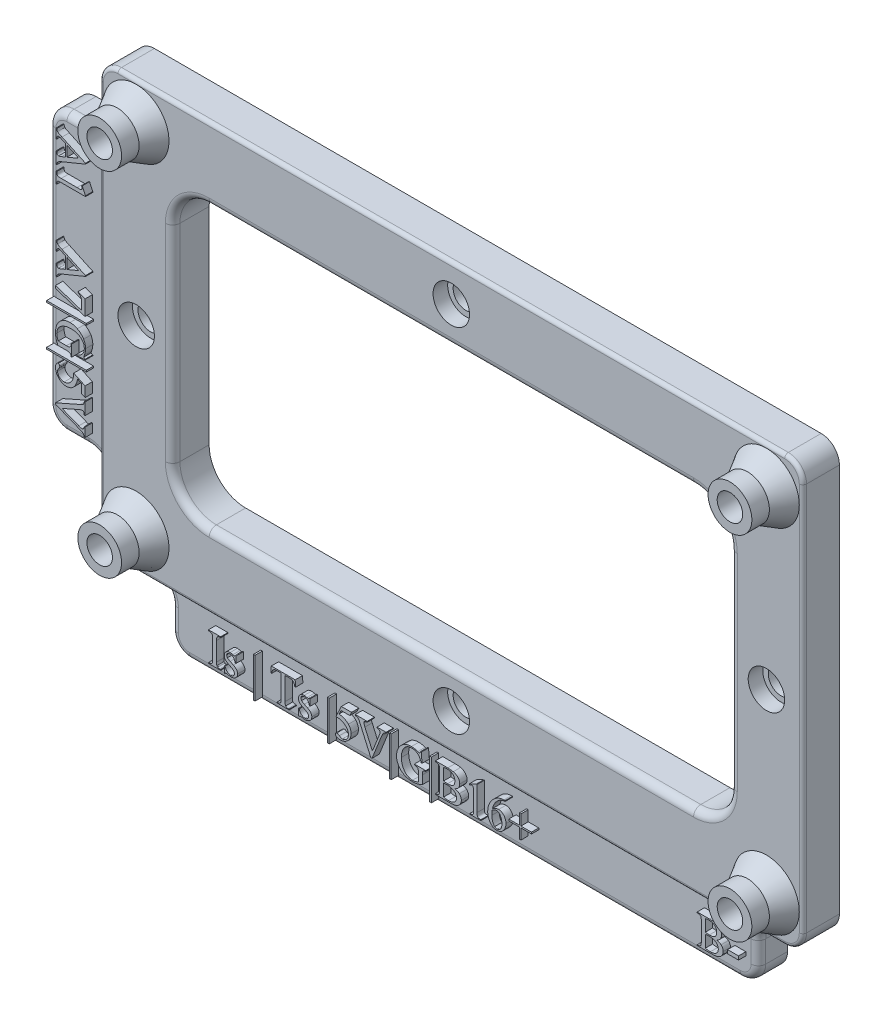
SolidWorks part; units mm, degrees
ref_plane "Front Plane" through (0, 0, 0) normal (0, 0, 1) x (1, 0, 0)
ref_plane "Top Plane" through (0, 0, 0) normal (0, 1, 0) x (1, 0, 0)
ref_plane "Right Plane" through (0, 0, 0) normal (1, 0, 0) x (0, 0, -1)
sketch "Sketch1" plane through (0, 0, 0) normal (0, 0, 1) x (1, 0, 0)
  line L0 (-5, 53.3) -> (91.4, 53.3)
  line L1 (91.4, 53.3) -> (91.4, -5)
  line L2 (91.4, -5) -> (-5, -5)
  line L3 (-5, -5) -> (-5, 53.3)
  line L4 (5, 43.3) -> (5, 5)
  line L5 (5, 5) -> (81.4, 5)
  line L6 (81.4, 5) -> (81.4, 43.3)
  line L7 (81.4, 43.3) -> (5, 43.3)
  circle A0 centre (0, 0) radius 1.75
  circle A1 centre (86.4, 0) radius 1.75
  circle A2 centre (0, 48.3) radius 1.75
  circle A3 centre (86.4, 48.3) radius 1.75
  circle A4 centre (0, 24.15) radius 1.75
  circle A5 centre (43.2, 48.3) radius 1.75
  circle A6 centre (86.4, 24.15) radius 1.75
  circle A7 centre (43.2, 0) radius 1.75
  point P26 (-5, 24.15)
  point P28 (43.2, 53.3)
  point P30 (43.2, -5)
  point P32 (91.4, 24.15)
  dimension "D1" = 3.5
  dimension "D2" = 3.5
  dimension "D3" = 3.5
  dimension "D4" = 3.5
  dimension "D15" = 3.5
  dimension "D16" = 3.5
  dimension "D17" = 3.5
  dimension "D18" = 3.5
  dimension "D5" = 86.4
  dimension "D6" = 48.3
  dimension "D7" = 5
  dimension "D8" = 5
  dimension "D9" = 5
  dimension "D10" = 5
  dimension "D11" = 10
  dimension "D12" = 10
  dimension "D13" = 10
  dimension "D14" = 10
  dimension "D19" = 5
  dimension "D20" = 5
  dimension "D21" = 5
  dimension "D22" = 5
extrude "Boss-Extrude1" add sketch "Sketch1" along normal blind 5
sketch "Sketch2" plane through (0, 0, 5) normal (0, 0, 1) x (1, 0, 0)
  circle A0 centre (0, 48.3) radius 1.75
  circle A1 centre (0, 48.3) radius 3
  circle A2 centre (86.4, 48.3) radius 1.75
  circle A3 centre (86.4, 48.3) radius 3
  circle A4 centre (86.4, 0) radius 1.75
  circle A5 centre (86.4, 0) radius 3
  circle A6 centre (0, 0) radius 1.75
  circle A7 centre (0, 0) radius 3
  dimension "D1" = 3.5
  dimension "D2" = 3.5
  dimension "D3" = 3.5
  dimension "D4" = 3.5
  dimension "D5" = 6
  dimension "D6" = 6
  dimension "D7" = 6
  dimension "D8" = 6
extrude "Boss-Extrude2" add sketch "Sketch2" along normal blind 5
sketch "Sketch3" plane through (0, 0, 0) normal (0, 0, 1) x (1, 0, 0)
  line L1 (-5, -5) -> (91.4, -5) construction
  line L14 (84.3, -5) -> (84.3, -13)
  line L15 (84.3, -13) -> (3.8, -13)
  line L16 (3.8, -13) -> (3.8, -5)
  line L18 (-5, 53.3) -> (-5, -5) construction
  line L27 (-5, 43.6) -> (-13, 43.6)
  line L28 (-13, 43.6) -> (-13, 5.6)
  line L29 (-13, 5.6) -> (-5, 5.6)
  line L30 (3.8, -5) -> (84.3, -5)
  line L31 (-5, 43.6) -> (-5, 5.6)
  circle A0 centre (0, 0) radius 1.75 construction
  dimension "D10" = 5.6
  dimension "D2" = 8
  dimension "D3" = 80.5
  dimension "D4" = 38
  dimension "D5" = 3.8
  dimension "D6" = 8
sketch "Sketch4" plane through (0, 0, 5) normal (0, 0, 1) x (1, 0, 0)
  circle A0 centre (0, 24.15) radius 2.5
  circle A1 centre (43.2, 48.3) radius 2.5
  circle A2 centre (86.4, 24.15) radius 2.5
  circle A3 centre (43.2, 0) radius 2.5
  dimension "D1" = 5
  dimension "D2" = 5
  dimension "D3" = 5
  dimension "D4" = 5
extrude "Cut-Extrude1" cut sketch "Sketch4" against normal blind 2
chamfer "Chamfer1" distance 1.5 angle 60 4 edges at (83.4, 48.3, 5) (83.4, 0, 5) (-3, 0, 5) (-3, 48.3, 5) first distance on face at (2.5, 24.15, 5)
extrude "Boss-Extrude3" add sketch "Sketch3" along normal blind 4
sketch "Sketch6" plane through (0, 0, 4) normal (0, 0, 1) x (1, 0, 0)
  line L0 (3.8, -11) -> (84.3, -11) construction
  line L3 (-11, 43.6) -> (-11, 5.6) construction
  line L6 (3.8, -13) -> (84.3, -13) construction
  line L7 (-13, 43.6) -> (-13, 5.6) construction
  text T0 "    Is | Ts |5V|G|B16+               B-" font "Times New Roman" height 4
  text T1 " A1    A7|G|5V" font "Times New Roman" height 4
  dimension "D1" = 2
  dimension "D2" = 2
extrude "Boss-Extrude4" add sketch "Sketch6" along normal blind 1 and the other way blind 2
fillet "Fillet1" radius 2.5 12 edges at (-13, 43.6, 2) (-5, 43.6, 2) (-5, 53.3, 2.5) (91.4, 53.3, 2.5) (91.4, -5, 2.5) (84.3, -5, 2) (84.3, -13, 2) (-13, 5.6, 2) (-5, 5.6, 2) (-5, -5, 2.5) (3.8, -5, 2) (3.8, -13, 2)
fillet "Fillet2" radius 5 4 edges at (5, 5, 2.5) (5, 43.3, 2.5) (81.4, 5, 2.5) (81.4, 43.3, 2.5)
fillet "Fillet3" radius 1 22 edges at (79.9355, 41.8355, 5) (81.4, 24.15, 5) (79.9355, 6.4645, 5) (43.2, 5, 5) (6.4645, 6.4645, 5) (5, 24.15, 5) (6.4645, 41.8355, 5) (-5.7322, 44.3322, 4) (-9, 43.6, 4) (-12.2678, 42.8678, 4) (-5.7322, 4.8678, 4) (-9, 5.6, 4) (-12.2678, 6.3322, 4) (3.0678, -5.7322, 4) (3.8, -9, 4) (4.5322, -12.2678, 4) (85.0322, -5.7322, 4) (84.3, -9, 4) (83.5678, -12.2678, 4) (43.2, 43.3, 5) (-13, 24.6, 4) (44.05, -13, 4)
fillet "Fillet4" radius 0.5 14 edges at (-5, 4.7614, 3.867) (-5, 44.4386, 3.867) (-4.2678, -4.2678, 5) (-5, 24.15, 5) (-4.2678, 52.5678, 5) (43.2, 53.3, 5) (90.6678, 52.5678, 5) (91.4, 24.15, 5) (90.6678, -4.2678, 5) (85.1386, -5, 3.867) (2.9614, -5, 3.867) (-5, 24.6, 4) (43.2, -5, 5) (44.05, -5, 4)
